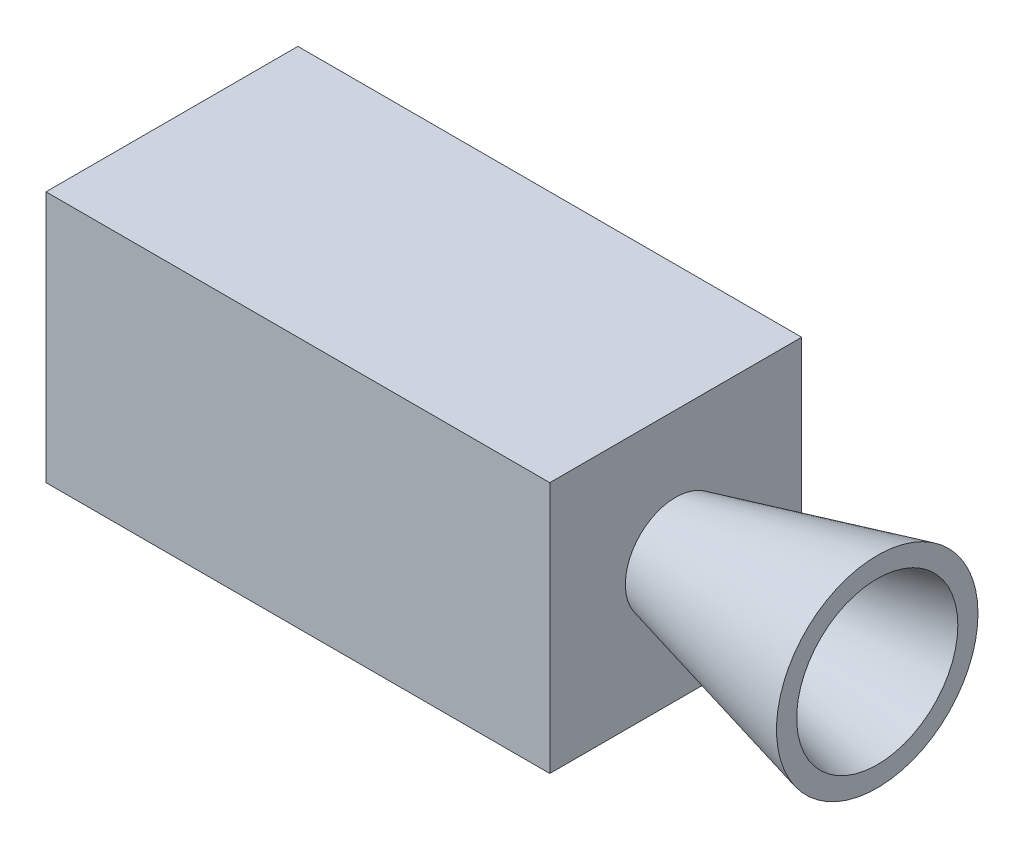
SolidWorks part; units mm, degrees
material "Alloy Steel"
ref_plane "Front Plane" through (0, 0, 0) normal (0, 0, 1) x (1, 0, 0)
ref_plane "Top Plane" through (0, 0, 0) normal (0, 1, 0) x (1, 0, 0)
ref_plane "Right Plane" through (0, 0, 0) normal (1, 0, 0) x (0, 0, -1)
sketch "Sketch1" plane through (0, 0, 0) normal (0, 0, 1) x (1, 0, 0)
  line L1 (0, 250) -> (1000, 250)
  line L2 (0, 250) -> (0, -250)
  line L3 (0, -250) -> (1000, -250)
  line L4 (1000, 250) -> (1000, -250)
  point P6 (0, 0)
  point P8 (0, 0)
  dimension "D1" = 1000
  dimension "D2" = 500
extrude "Boss-Extrude1" add sketch "Sketch1" along normal blind 250 and the other way blind 250
sketch "Sketch2" plane through (1000, 0, 0) normal (1, 0, 0) x (0, 0, -1)
  point P0 (0, 0)
sketch "Sketch3" plane through (0, 0, 0) normal (0, 0, 1) x (1, 0, 0)
  line L0 (1000, 0) -> (1000, 100)
  line L1 (1000, -250) -> (1000, 250) construction
  line L2 (1000, 100) -> (1400, 200)
  line L3 (1400, 200) -> (1400, 160)
  line L4 (1400, 160) -> (1040, 70)
  line L5 (1040, 70) -> (1040, 0)
  line L6 (1040, 0) -> (1000, 0)
  point P8 (0, 0)
  point P10 (0, 0)
  dimension "D1" = 100
  dimension "D2" = 70
  dimension "D3" = 40
  dimension "D4" = 400
  dimension "D5" = 40
revolve "Revolve1" add sketch "Sketch3" angle 360 about L6
